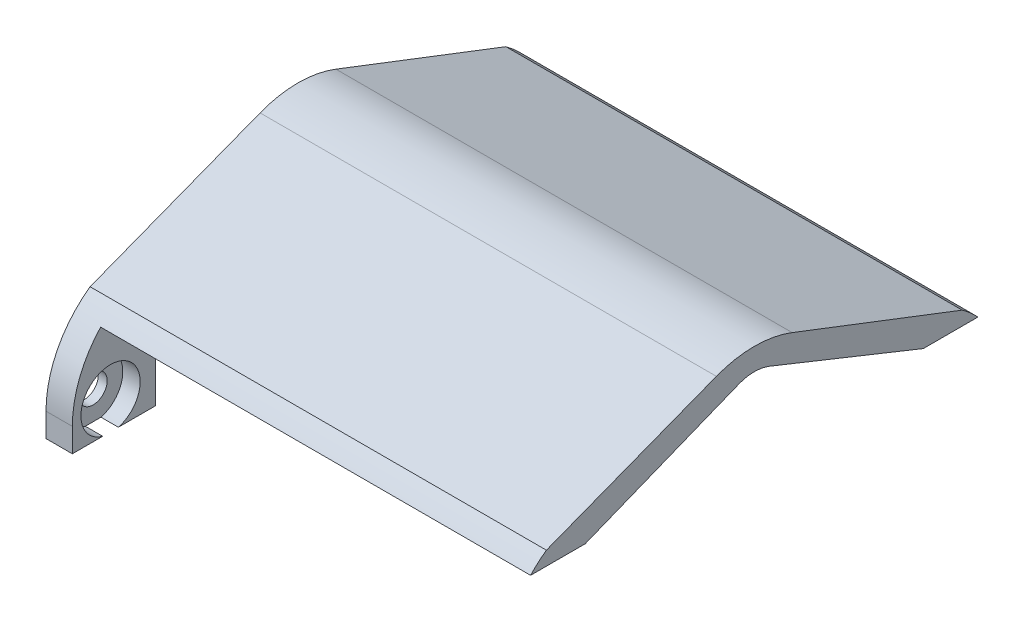
SolidWorks part; units mm, degrees
ref_plane "Front Plane" through (0, 0, 0) normal (0, 0, 1) x (1, 0, 0)
ref_plane "Top Plane" through (0, 0, 0) normal (0, 1, 0) x (1, 0, 0)
ref_plane "Right Plane" through (0, 0, 0) normal (1, 0, 0) x (0, 0, -1)
sketch "Sketch1" plane through (0, 0, 0) normal (1, 0, 0) x (0, 0, -1)
  line L0 (0, 0) -> (20, 0)
  line L1 (0, 0) -> (0, 26.3957)
  line L2 (101.4959, 0) -> (121.4959, 0)
  line L3 (20, 0) -> (20, 23.0489)
  line L4 (20, 23.0489) -> (60.748, 39.3662)
  line L5 (121.4959, 0) -> (121.4959, 26.3957)
  line L6 (101.4959, 23.0489) -> (101.4959, 0)
  line L7 (101.4959, 23.0489) -> (60.748, 39.3662)
  line L9 (0, 26.3957) -> (10.63, 26.3957)
  line L10 (121.4959, 26.3957) -> (110.8659, 26.3957)
  line L11 (10.63, 26.3957) -> (60.748, 45.7162)
  line L12 (110.8659, 26.3957) -> (60.748, 45.7162)
extrude "Boss-Extrude1" add sketch "Sketch1" along normal blind 110 contours L9 L11 L12 L10 L5 L2 L6 L7 L4 L3 L0 L1
fillet "Fillet1" radius 25.4 3 edges at (55, 26.3957, -121.4959) (55, 26.3957, 0) (55, 45.7162, -60.748)
fillet "Fillet2" radius 10 1 edges at (55, 39.3662, -60.748)
sketch "Sketch2" plane through (110, 0, 0) normal (1, 0, 0) x (0, 0, -1)
  line L0 (20, 0) -> (0, 0)
  line L1 (20, 0) -> (20, 23.0489)
  line L2 (20, 23.0489) -> (0, 23.0489)
  line L3 (0, 23.0489) -> (0, 0)
  line L4 (101.4959, 23.0489) -> (121.4959, 23.0489)
  line L5 (121.4959, 23.0489) -> (121.4959, 0)
  line L6 (121.4959, 0) -> (101.4959, 0)
  line L7 (101.4959, 0) -> (101.4959, 23.0489)
extrude "Cut-Extrude1" cut sketch "Sketch2" against normal blind 103.65
hole_wizard "CBORE for 1/4 Binding Head Machine Screw1" positions "Sketch4" profile "Sketch3" counterbore size "1/4" standard "ANSI Inch" end condition through all
sketch "Sketch4" plane through (6.35, 0, 0) normal (1, 0, 0) x (0, 0, -1)
  line L0 (20, 0) -> (20, 23.0489) construction
  line L1 (0, 0) -> (20, 0) construction
  line L2 (101.4959, 0) -> (121.4959, 0) construction
  line L3 (101.4959, 23.0489) -> (101.4959, 0) construction
  point P0 (9.21, 6.89)
  point P2 (112.2859, 6.89)
  dimension "D1" = 10.79
  dimension "D2" = 6.89
  dimension "D3" = 6.89
  dimension "D4" = 10.79
sketch "Sketch3" plane through (6.35, 6.89, -9.21) normal (0, 1, 0) x (0, 0, -1)
  line L0 (0, 0) -> (0, 6.35)
  line L1 (0, 6.35) -> (3.3782, 6.35)
  line L3 (3.3782, 6.35) -> (3.3782, 4.191)
  line L4 (3.3782, 4.191) -> (7.1437, 4.191)
  line L5 (7.1437, 4.191) -> (7.1437, 0)
  line L7 (7.1437, 0) -> (0, 0)
  line L11 (0, -6.35) -> (0, 107.95) construction
  dimension "Thru Hole Dia." = 6.7564
  dimension "Thru Hole Depth" = 6.35
  dimension "C'Bore Dia." = 14.2875
  dimension "C'Bore Depth" = 4.191
